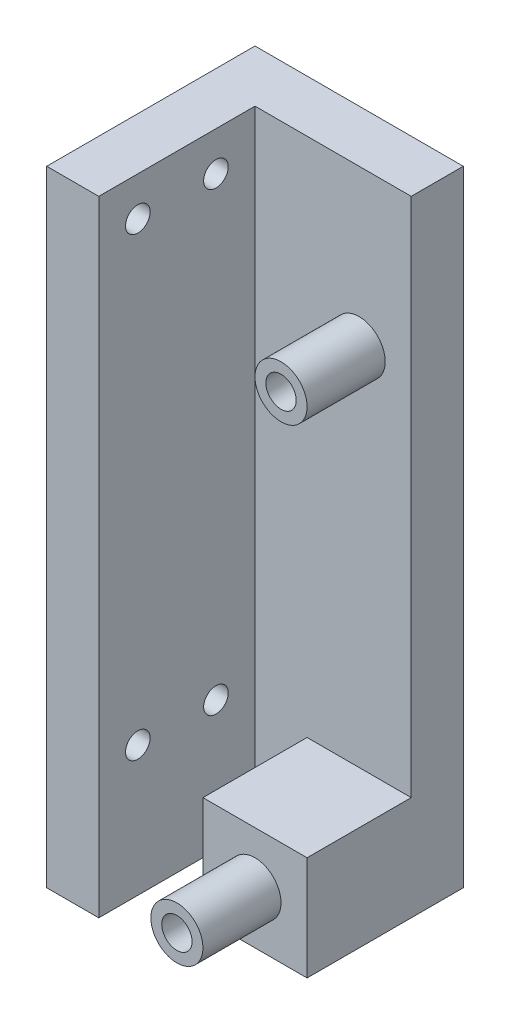
SolidWorks part; units mm, degrees
ref_plane "Front Plane" through (0, 0, 0) normal (0, 0, 1) x (1, 0, 0)
ref_plane "Top Plane" through (0, 0, 0) normal (0, 1, 0) x (1, 0, 0)
ref_plane "Right Plane" through (0, 0, 0) normal (1, 0, 0) x (0, 0, -1)
sketch "Sketch1" plane through (0, 0, 0) normal (0, 0, 1) x (1, 0, 0)
  line L1 (0, 0) -> (25.4, 0)
  line L2 (0, 0) -> (0, 76.2)
  line L3 (0, 76.2) -> (25.4, 76.2)
  line L4 (25.4, 0) -> (25.4, 76.2)
  dimension "D1" = 76.2
  dimension "D2" = 25.4
extrude "Boss-Extrude1" add sketch "Sketch1" against normal blind 25.4
sketch "Sketch10" plane through (25.4, 0, 0) normal (1, 0, 0) x (0, 0, -1)
  line L0 (25.4, 76.2) -> (0, 76.2) construction
  line L1 (19.05, 76.2) -> (0, 76.2)
  line L2 (19.05, 76.2) -> (19.05, 0)
  line L3 (19.05, 0) -> (0, 0)
  line L4 (0, 76.2) -> (0, 0)
  line L5 (25.4, 0) -> (0, 0) construction
  line L6 (25.4, 0) -> (25.4, 76.2) construction
  line L8 (0, 0) -> (0, 76.2) construction
  dimension "D1" = 6.35
extrude "Cut-Extrude5" cut sketch "Sketch10" against normal offset from surface (19.05 mm away) 6.35 up to face at (0, 38.1, -12.7)
sketch "Sketch12" plane through (0, 0, -25.4) normal (0, 0, -1) x (-1, 0, 0)
  line L0 (-25.4, 76.2) -> (0, 76.2) construction
  line L1 (-25.4, 0) -> (-25.4, 76.2) construction
  circle A1 centre (-19.05, 57.15) radius 3.175
  circle A2 centre (-19.05, 57.15) radius 1.85
  dimension "D2" = 6.35
  dimension "D4" = 3.7
  dimension "D1" = 19.05
  dimension "D3" = 6.35
extrude "Boss-Extrude2" add sketch "Sketch12" against normal blind 9.525 from surface starting at face at (15.875, 38.1, -19.05)
sketch "Sketch13" plane through (0, 0, -25.4) normal (0, 0, -1) x (-1, 0, 0)
  line L1 (-25.4, 0) -> (-12.7, 0)
  line L3 (-25.4, 12.7) -> (-12.7, 12.7)
  line L4 (-12.7, 0) -> (-12.7, 12.7)
  line L5 (-25.4, 12.7) -> (-25.4, 0)
  dimension "D2" = 12.7
  dimension "D3" = 12.7
extrude "Boss-Extrude3" add sketch "Sketch13" against normal blind 12.7 from surface starting at face at (19.05, 60.325, -19.05)
sketch "Sketch14" plane through (0, 0, -6.35) normal (0, 0, 1) x (1, 0, 0)
  line L1 (25.4, 0) -> (12.7, 0) construction
  line L2 (25.4, 12.7) -> (25.4, 76.2) construction
  circle A0 centre (19.05, 6.35) radius 1.85
  circle A1 centre (19.05, 6.35) radius 3.175
  circle A3 centre (19.05, 57.15) radius 1.85 construction
  circle A4 centre (19.05, 57.15) radius 3.175 construction
  dimension "D1" = 6.35
  dimension "D2" = 6.35
extrude "Boss-Extrude4" add sketch "Sketch14" along normal blind 9.525
sketch "Sketch15" plane through (6.35, 0, 0) normal (1, 0, 0) x (0, 0, -1)
  line L1 (19.05, 76.2) -> (0, 76.2) construction
  line L2 (0, 76.2) -> (0, 0) construction
  line L3 (19.05, 12.7) -> (19.05, 76.2) construction
  line L4 (0, 0) -> (19.05, 0) construction
  line L5 (25.4, 0) -> (6.35, 0) construction
  circle A0 centre (4.7625, 71.4375) radius 1.5
  circle A1 centre (14.2875, 71.4375) radius 1.5
  circle A2 centre (4.7625, 15.875) radius 1.5
  circle A3 centre (14.2875, 15.875) radius 1.5
  dimension "D1" = 3
  dimension "D2" = 4.7625
  dimension "D3" = 4.7625
  dimension "D4" = 4.7625
  dimension "D5" = 15.875
  dimension "D6" = 15.875
extrude "Cut-Extrude6" cut sketch "Sketch15" against normal through all
equation "\"D4@Sketch12\"= 3.7mm"
equation "\"D1@Boss-Extrude1\"=(0.375+15.7mm)+0.25+0.25"
equation "\"tightTol\"= 0.005in"
equation "\"normTol\"= 0.01in"
equation "\"looseTol\"= 0.02in"
equation "\"D1@Sketch15\"=3mm"
